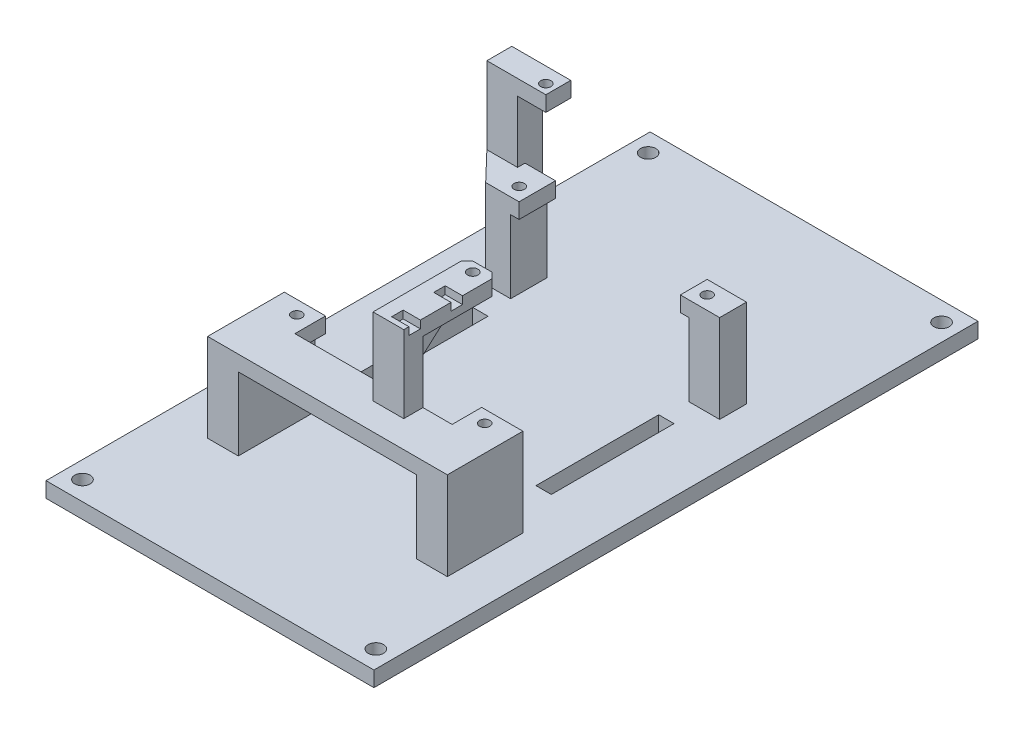
SolidWorks part; units mm, degrees
ref_plane "Front Plane" through (0, 0, 0) normal (0, 0, 1) x (1, 0, 0)
ref_plane "Top Plane" through (0, 0, 0) normal (0, 1, 0) x (1, 0, 0)
ref_plane "Right Plane" through (0, 0, 0) normal (1, 0, 0) x (0, 0, -1)
sketch "Sketch1" plane through (0, 0, 0) normal (0, 1, 0) x (1, 0, 0)
  line L1 (-42.75, 78.75) -> (42.75, 78.75)
  line L2 (-42.75, 78.75) -> (-42.75, -78.75)
  line L3 (-42.75, -78.75) -> (42.75, -78.75)
  line L4 (42.75, 78.75) -> (42.75, -78.75)
  line L5 (-42.75, 78.75) -> (42.75, -78.75) construction
  line L6 (-42.75, -78.75) -> (42.75, 78.75) construction
  point P0 (0, 0)
  dimension "D1" = 157.5
  dimension "D2" = 85.5
extrude "Boss-Extrude1" add sketch "Sketch1" along normal blind 4
sketch "Sketch2" plane through (0, 4, 0) normal (0, 1, 0) x (1, 0, 0)
  line L0 (-42.75, -78.75) -> (42.75, -78.75) construction
  line L1 (42.75, -78.75) -> (42.75, 78.75) construction
  line L2 (0, 0) -> (50000, 0) construction
  line L3 (0, 0) -> (0, -50000) construction
  circle A0 centre (38.25, -73.75) radius 2
  circle A1 centre (38.25, 73.75) radius 2
  circle A2 centre (-38.25, -73.75) radius 2
  circle A3 centre (-38.25, 73.75) radius 2
  dimension "D1" = 4
  dimension "D2" = 5
  dimension "D3" = 4.5
extrude "Cut-Extrude1" cut sketch "Sketch2" against normal up to next
sketch "Sketch5" plane through (0, 4, 0) normal (0, 1, 0) x (1, 0, 0)
  line L0 (-24.5, 26.3886) -> (-24.5, -31.6114) construction
  line L1 (-24.5, -31.6114) -> (24.5, -31.6114) construction
  line L2 (24.5, -31.6114) -> (24.5, 26.3886) construction
  line L3 (24.5, 26.3886) -> (-24.5, 26.3886) construction
  line L4 (0, 49.8886) -> (0, -35.1114) construction
  line L5 (-22.25, 67.25) -> (22.25, 67.25) construction
  line L6 (-22.25, 67.25) -> (-22.25, -67.25) construction
  line L7 (-22.25, -67.25) -> (22.25, -67.25) construction
  line L8 (22.25, 67.25) -> (22.25, -67.25) construction
  line L9 (-22.25, 67.25) -> (22.25, -67.25) construction
  line L10 (-22.25, -67.25) -> (22.25, 67.25) construction
  line L11 (-28, 49.8886) -> (28, 49.8886) construction
  line L12 (-28, 49.8886) -> (-28, -35.1114) construction
  line L13 (-28, -35.1114) -> (28, -35.1114) construction
  line L14 (28, 49.8886) -> (28, -35.1114) construction
  line L15 (24.5, 26.3886) -> (23.25, 26.3886) construction
  line L16 (-37, 36.9499) -> (-29, 36.9499)
  line L18 (-29.75, 22.8886) -> (-23.25, 22.8886)
  line L19 (-23.25, 32.3886) -> (-23.25, 22.8886)
  line L20 (23.25, 29.8886) -> (31.25, 29.8886)
  line L21 (23.25, 29.8886) -> (23.25, 22.8886)
  line L22 (23.25, 22.8886) -> (31.25, 22.8886)
  line L23 (31.25, 29.8886) -> (31.25, 22.8886)
  line L24 (-23.25, -48.1114) -> (23.25, -48.1114) construction
  line L25 (-31.25, -28.1114) -> (-23.25, -28.1114)
  line L26 (-31.25, -28.1114) -> (-31.25, -48.1114)
  line L27 (-31.25, -48.1114) -> (-23.25, -48.1114)
  line L28 (-23.25, -28.1114) -> (-23.25, -48.1114)
  line L29 (23.25, -28.4114) -> (31.25, -28.4114)
  line L30 (23.25, -28.4114) -> (23.25, -48.1114)
  line L31 (23.25, -48.1114) -> (31.25, -48.1114)
  line L32 (31.25, -28.4114) -> (31.25, -48.1114)
  line L33 (22.25, -16) -> (26.25, -16)
  line L34 (-22.25, -16) -> (-26.25, -16)
  line L35 (-22.25, -16) -> (-22.25, 16)
  line L36 (-22.25, 16) -> (-26.25, 16)
  line L37 (-26.25, -16) -> (-26.25, 16)
  line L38 (22.25, -16) -> (22.25, 16)
  line L39 (26.25, -16) -> (26.25, 16)
  line L40 (22.25, 16) -> (26.25, 16)
  line L41 (-23.25, 32.3886) -> (-29, 32.3886)
  line L42 (-29, 32.3886) -> (-29, 36.9499)
  line L43 (-37, 36.9499) -> (-37, 30.4499)
  line L44 (-37, 30.4499) -> (-29.75, 22.8886)
  circle A0 centre (-24.5, 26.3886) radius 1.35
  circle A1 centre (-24.13, 32.9499) radius 1.35
  circle A2 centre (8.89, -19.1201) radius 1.35
  circle A3 centre (24.5, -31.6114) radius 1.35
  circle A4 centre (24.5, 26.3886) radius 1.35
  circle A5 centre (-24.5, -31.6114) radius 1.35
  point P9 (0, 0)
  point P32 (23.25, 26.3886)
  point P46 (-22.25, 0)
  dimension "D1" = 24.5
  dimension "D2" = 26.3886
  dimension "D3" = 32.9499
  dimension "D4" = 24.13
  dimension "D5" = 2.7
  dimension "D6" = 33.02
  dimension "D7" = 52.07
  dimension "D8" = 49
  dimension "D9" = 58
  dimension "D18" = 4
  dimension "D21" = 3.5
  dimension "D24" = 3.5
  dimension "D10" = 44.5
  dimension "D11" = 134.5
  dimension "D12" = 56
  dimension "D13" = 85
  dimension "D14" = 28
  dimension "D15" = 3.5
  dimension "D16" = 1
  dimension "D17" = 3.5
  dimension "D19" = 6.5
  dimension "D20" = 1
  dimension "D22" = 8
  dimension "D23" = 1
  dimension "D25" = 1
  dimension "D26" = 3.2
  dimension "D27" = 8
  dimension "D28" = 8
  dimension "D29" = 20
  dimension "D30" = 32
  dimension "D31" = 4
  dimension "D32" = 6
  dimension "D33" = 1
  dimension "D34" = 8
  dimension "D35" = 6.5
extrude "Cut-Extrude3" cut sketch "Sketch5" against normal up to next contours L37 L34 L35 L36 | L39 L40 L38 L33 region at (-24.25, 4, 0)
extrude "Boss-Extrude3" add sketch "Sketch5<3>" along normal blind 23 contours L32 L29 L30 L31 | L28 L25 L26 L27 | L23 L20 L21 L22 | L43 L44 L18 L19 L41 L42 L16 | L28 A5 | L30 A3 | L21 A4 | L19 A0 | L41 A1 L19 region at (-30.2918, 4, -30.0416) region at (-24.2016, 4, -32.0522) region at (-24.5156, 4, -26.3886) region at (27.5573, 4, -26.3886) region at (24.5156, 4, -26.3886) region at (-27.3502, 4, 38.3496) region at (-24.5156, 4, 31.6114) region at (27.3518, 4, 38.509) region at (24.5156, 4, 31.6114)
sketch "Sketch5<3>" plane through (0, 4, 0) normal (0, 1, 0) x (1, 0, 0) same geometry as "Sketch5"
sketch "Sketch6" plane through (-23.25, 0, 0) normal (1, 0, 0) x (0, 0, -1)
  line L0 (-28.1114, 27) -> (-28.1114, 4) construction
  line L1 (-48.1114, 27) -> (-28.1114, 27)
  line L2 (-48.1114, 27) -> (-48.1114, 23)
  line L3 (-48.1114, 23) -> (-28.1114, 23)
  line L4 (-28.1114, 27) -> (-28.1114, 23)
  line L5 (-28.1114, 4) -> (-48.1114, 4) construction
  dimension "D1" = 19
extrude "Boss-Extrude5" add sketch "Sketch6" along normal up to surface (46.5 mm away) up to face at (23.25, 15.5, 38.2614)
sketch "Sketch7" plane through (0, 27, 0) normal (0, 1, 0) x (1, 0, 0)
  line L0 (-31.25, -28.1114) -> (23.25, -28.1114) construction
  line L1 (-20.5, -28.1114) -> (23.25, -28.1114)
  line L2 (-20.5, -28.1114) -> (-20.5, -36.1114)
  line L3 (-20.5, -36.1114) -> (20.5, -36.1114)
  line L4 (20.5, -28.4114) -> (20.5, -36.1114)
  line L5 (23.25, -28.4114) -> (20.5, -28.4114)
  line L6 (23.25, -28.1114) -> (23.25, -28.4114)
  line L7 (-31.25, -28.1114) -> (-31.25, -48.1114) construction
  line L8 (31.25, -28.4114) -> (31.25, -48.1114) construction
  dimension "D1" = 10.75
  dimension "D2" = 10.75
  dimension "D3" = 8
extrude "Cut-Extrude4" cut sketch "Sketch7" against normal up to next
sketch "Sketch8" plane through (23.25, 0, 0) normal (-1, 0, 0) x (0, 0, 1)
  line L0 (-22.8886, 27) -> (-22.8886, 4) construction
  line L1 (-29.8886, 27) -> (-22.8886, 27)
  line L2 (-29.8886, 27) -> (-29.8886, 23)
  line L3 (-29.8886, 23) -> (-22.8886, 23)
  line L4 (-22.8886, 27) -> (-22.8886, 23)
  line L5 (-29.8886, 4) -> (-22.8886, 4) construction
  dimension "D1" = 19
extrude "Boss-Extrude6" add sketch "Sketch8" along normal blind 2.25
sketch "Sketch9" plane through (-23.25, 0, 0) normal (1, 0, 0) x (0, 0, -1)
  line L0 (32.3886, 27) -> (32.3886, 4) construction
  line L1 (22.8886, 27) -> (32.3886, 27)
  line L2 (22.8886, 27) -> (22.8886, 23)
  line L3 (22.8886, 23) -> (32.3886, 23)
  line L4 (32.3886, 27) -> (32.3886, 23)
  line L5 (32.3886, 4) -> (22.8886, 4) construction
  dimension "D1" = 19
extrude "Boss-Extrude7" add sketch "Sketch9" along normal blind 2.2
extrude "Cut-Extrude5" cut sketch "Sketch5<5>" against normal blind 3.5 from surface contours A0 | A4 | A3 | A5 starting at face at (0, 27, 35.1864)
sketch "Sketch5<5>" plane through (0, 4, 0) normal (0, 1, 0) x (1, 0, 0) same geometry as "Sketch5"
sketch "Sketch13" plane through (0, 27, 0) normal (0, 1, 0) x (1, 0, 0)
  line L0 (-29, 32.3886) -> (-29, 36.9499) construction
  line L1 (-37, 36.9499) -> (-29, 36.9499)
  line L2 (-37, 36.9499) -> (-37, 30.4499)
  line L3 (-37, 30.4499) -> (-29, 30.4499)
  line L4 (-29, 36.9499) -> (-29, 30.4499)
  line L5 (-20.5, -36.1114) -> (20.5, -36.1114) construction
  line L6 (4.89, -36.1114) -> (12.89, -36.1114)
  line L7 (4.89, -36.1114) -> (4.89, -41.1114)
  line L8 (4.89, -41.1114) -> (12.89, -41.1114)
  line L9 (12.89, -36.1114) -> (12.89, -41.1114)
  line L10 (8.89, -19.1201) -> (8.89, -36.1114) construction
  circle A0 centre (-24.13, 32.9499) radius 1.35 construction
  point P15 (8.89, -36.1114)
  dimension "D1" = 2.5
  dimension "D2" = 5
  dimension "D3" = 8
extrude "Boss-Extrude8" add sketch "Sketch13" along normal blind 20.1
sketch "Sketch14" plane through (-29, 0, 0) normal (1, 0, 0) x (0, 0, -1)
  line L0 (36.9499, 47.1) -> (36.9499, 4) construction
  line L1 (30.4499, 47.1) -> (36.9499, 47.1)
  line L2 (30.4499, 47.1) -> (30.4499, 43.1)
  line L3 (30.4499, 43.1) -> (36.9499, 43.1)
  line L4 (36.9499, 47.1) -> (36.9499, 43.1)
  dimension "D1" = 4
extrude "Boss-Extrude9" add sketch "Sketch14" along normal blind 7.37
sketch "Sketch15" plane through (0, 0, 36.1114) normal (0, 0, -1) x (-1, 0, 0)
  line L0 (-4.89, 47.1) -> (-4.89, 27) construction
  line L1 (-12.89, 47.1) -> (-4.89, 47.1)
  line L2 (-12.89, 47.1) -> (-12.89, 43.1)
  line L3 (-12.89, 43.1) -> (-4.89, 43.1)
  line L4 (-4.89, 47.1) -> (-4.89, 43.1)
  dimension "D1" = 4
extrude "Boss-Extrude10" add sketch "Sketch15" along normal blind 19.4913
extrude "Cut-Extrude6" cut sketch "Sketch5<6>" against normal up to next from surface contours A2 | A1 starting at face at (-29.315, 47.1, -33.6999)
sketch "Sketch5<6>" plane through (0, 4, 0) normal (0, 1, 0) x (1, 0, 0) same geometry as "Sketch5"
sketch "Sketch16" plane through (0, 47.1, 0) normal (0, 1, 0) x (1, 0, 0)
  line L0 (8.89, -19.1201) -> (8.89, -27.2991) construction
  line L1 (8.89, -27.2991) -> (12.89, -27.2991) construction
  line L2 (12.89, -41.1114) -> (12.89, -16.6201) construction
  line L3 (8.39, -28.7991) -> (12.89, -28.7991)
  line L4 (8.39, -25.7991) -> (8.39, -28.7991)
  line L5 (8.39, -25.7991) -> (12.89, -25.7991)
  line L6 (8.39, -39.7721) -> (12.89, -39.7721)
  line L7 (8.89, -28.2991) -> (12.89, -28.2991) construction
  line L8 (8.89, -26.2991) -> (12.89, -26.2991) construction
  line L10 (8.89, -26.2991) -> (8.89, -28.2991) construction
  line L11 (8.89, -27.2991) -> (8.89, -38.2721) construction
  line L12 (8.89, -38.2721) -> (12.89, -38.2721) construction
  line L13 (12.89, -41.1114) -> (12.89, -36.1114) construction
  line L14 (8.89, -39.2721) -> (12.89, -39.2721) construction
  line L15 (8.89, -37.2721) -> (12.89, -37.2721) construction
  line L16 (8.89, -37.2721) -> (8.89, -39.2721) construction
  line L18 (8.39, -36.7721) -> (8.39, -39.7721)
  line L19 (8.39, -36.7721) -> (12.89, -36.7721)
  line L20 (12.89, -25.7991) -> (12.89, -28.7991)
  line L21 (12.89, -36.7721) -> (12.89, -39.7721)
  dimension "D1" = 8.179
  dimension "D2" = 1
  dimension "D4" = 10.973
  dimension "D5" = 1
  dimension "D7" = 0.5
  dimension "D3" = 1
  dimension "D6" = 1
extrude "Cut-Extrude7" cut sketch "Sketch16" against normal blind 2
chamfer "Chamfer1" distance 1.5 angle 45 2 edges at (4.89, 45.1, 16.6201) (12.89, 45.1, 16.6201)
ref_plane "Plane1" through (8.89, 0, 0) normal (-1, 0, 0) x (0, 0, 1)
sketch "Sketch19" plane through (8.89, 0, 0) normal (-1, 0, 0) x (0, 0, 1)
  line L0 (27.1157, 43.1) -> (36.1114, 35.05)
  line L1 (18.1201, 43.1) -> (36.1114, 43.1) construction
  line L2 (36.1114, 43.1) -> (36.1114, 27) construction
  line L3 (27.1157, 43.1) -> (36.1114, 43.1)
  line L4 (36.1114, 43.1) -> (36.1114, 35.05)
extrude "Boss-Extrude11" add sketch "Sketch19" along normal blind 2 and the other way blind 2
sketch "Sketch20" plane through (0, 0, -36.9499) normal (0, 0, -1) x (-1, 0, 0)
  line L1 (37, 4) -> (31.25, 4)
  line L2 (37, 4) -> (37, 10)
  line L3 (37, 10) -> (31.25, 10)
  line L4 (31.25, 4) -> (31.25, 10)
  dimension "D1" = 5.75
  dimension "D2" = 6
extrude "Cut-Extrude8" cut sketch "Sketch20" against normal up to next
chamfer "Chamfer2" distance 5.75 angle 45 1 edges at (-37, 10, -33.6999)
sketch "Sketch21" plane through (0, 0, -36.9499) normal (0, 0, -1) x (-1, 0, 0)
  line L1 (31.25, 10) -> (29, 10)
  line L2 (31.25, 10) -> (31.25, 4)
  line L3 (31.25, 4) -> (29, 4)
  line L4 (29, 10) -> (29, 4)
extrude "Cut-Extrude9" cut sketch "Sketch21" against normal up to surface (4.5613 mm away) up to face at (-24.4333, 18, -32.3886)
chamfer "Chamfer3" distance 5.75 distance2 4.5613 1 edges at (-30.125, 10, -36.9499) first distance on face at (-29.5014, 30.8786, -36.9499)
